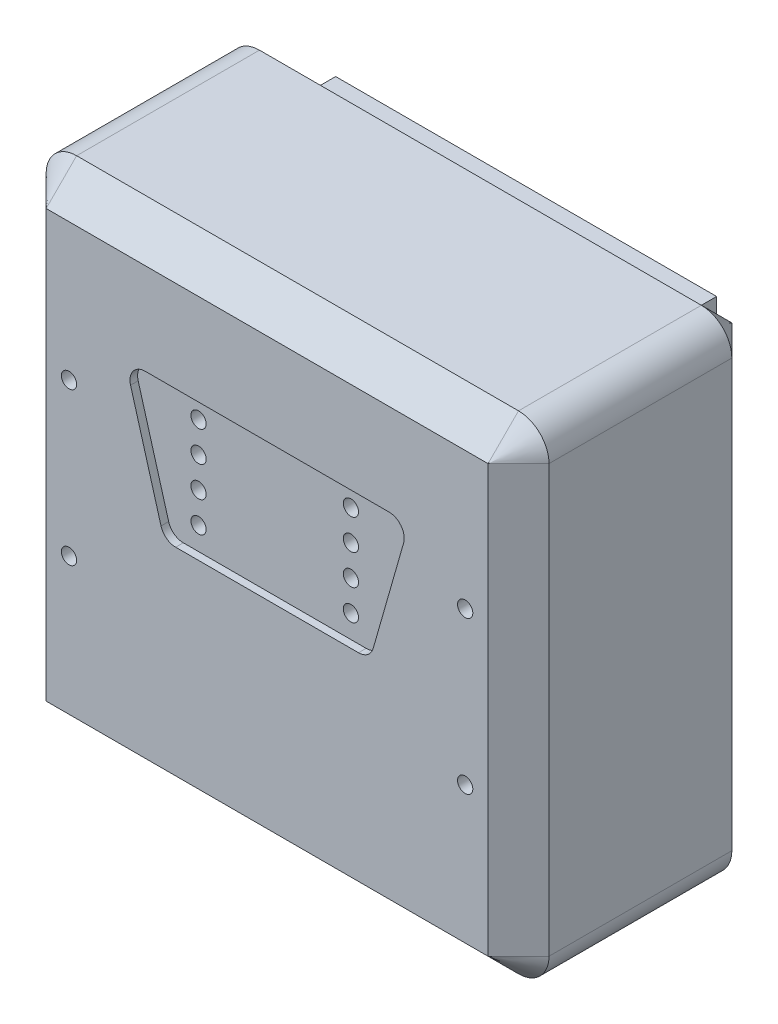
SolidWorks part; units mm, degrees
material "PE High Density Film"
ref_plane "Front Plane" through (0, 0, 0) normal (0, 0, 1) x (1, 0, 0)
ref_plane "Top Plane" through (0, 0, 0) normal (0, 1, 0) x (1, 0, 0)
ref_plane "Right Plane" through (0, 0, 0) normal (1, 0, 0) x (0, 0, -1)
sketch "Sketch1" plane through (0, 0, 0) normal (0, 0, 1) x (1, 0, 0)
  line L0 (0, 0) -> (0, 50.8) construction
  line L1 (-79.375, 50.8) -> (79.375, 50.8)
  line L2 (-79.375, 0) -> (79.375, 0)
  line L3 (79.375, 0) -> (79.375, 50.8)
  line L4 (28.575, 50.8) -> (28.575, 0) construction
  line L5 (28.575, 25.4) -> (79.375, 25.4) construction
  line L6 (53.975, 25.4) -> (53.975, 50.8) construction
  line L7 (53.975, 25.4) -> (53.975, 0) construction
  line L8 (-53.975, 25.4) -> (-53.975, 0) construction
  line L9 (-53.975, 25.4) -> (-53.975, 50.8) construction
  line L10 (-28.575, 25.4) -> (-79.375, 25.4) construction
  line L11 (-28.575, 50.8) -> (-28.575, 0) construction
  line L12 (-79.375, 0) -> (-79.375, 50.8)
  circle A2 centre (53.975, 38.1) radius 1.5875
  circle A3 centre (53.975, 12.7) radius 1.5875
  circle A4 centre (-53.975, 12.7) radius 1.5875
  circle A5 centre (-53.975, 38.1) radius 1.5875
  circle A6 centre (0, 25.4) radius 1.5875
  dimension "D4" = 3.175
  dimension "D5" = 3.175
  dimension "D1" = 50.8
  dimension "D2" = 28.575
  dimension "D3" = 50.8
extrude "Boss-Extrude1" add sketch "Sketch1" along normal blind 6.35
sketch "Sketch2" plane through (0, 0, 6.35) normal (0, 0, 1) x (1, 0, 0)
  line L0 (79.375, 50.8) -> (-79.375, 50.8) construction
  line L1 (-92.075, -139.7) -> (92.075, -139.7)
  line L2 (-104.775, -127) -> (-104.775, 50.8)
  line L3 (-92.075, 63.5) -> (92.075, 63.5)
  line L4 (104.775, -127) -> (104.775, 50.8)
  line L5 (-79.375, 50.8) -> (-79.375, 0) construction
  line L6 (79.375, 0) -> (79.375, 50.8) construction
  arc A0 (-92.075, -139.7) -> (-104.775, -127) centre (-92.075, -127) cw
  arc A1 (92.075, -139.7) -> (104.775, -127) centre (92.075, -127) ccw
  arc A2 (92.075, 63.5) -> (104.775, 50.8) centre (92.075, 50.8) cw
  arc A3 (-104.775, 50.8) -> (-92.075, 63.5) centre (-92.075, 50.8) cw
  point P12 (-104.775, -139.7)
  point P19 (-104.775, 63.5)
  dimension "D5" = 12.7
  dimension "D1" = 12.7
  dimension "D2" = 25.4
  dimension "D3" = 25.4
  dimension "D4" = 203.2
extrude "Boss-Extrude2" add sketch "Sketch2" along normal blind 101.6
chamfer "Chamfer1" distance 12.7 angle 45 16 edges at (0, 63.5, 107.95) (-101.0553, 59.7803, 107.95) (101.0553, 59.7803, 107.95) (-104.775, -38.1, 107.95) (104.775, -38.1, 107.95) (-101.0553, -135.9803, 107.95) (101.0553, -135.9803, 107.95) (0, -139.7, 107.95) (-104.775, -38.1, 6.35) (-101.0553, -135.9803, 6.35) (-101.0553, 59.7803, 6.35) (0, -139.7, 6.35) (0, 63.5, 6.35) (101.0553, -135.9803, 6.35) (101.0553, 59.7803, 6.35) (104.775, -38.1, 6.35)
sketch "Sketch3" plane through (0, 0, 107.95) normal (0, 0, 1) x (1, 0, 0)
  line L0 (0, -127) -> (0, 50.8) construction
  line L1 (-92.075, -127) -> (92.075, -127) construction
  line L2 (92.075, 50.8) -> (-92.075, 50.8) construction
  line L3 (92.075, -38.1) -> (-92.075, -38.1) construction
  line L4 (-92.075, 50.8) -> (-92.075, -127) construction
  circle A0 centre (-82.55, -6.35) radius 3.175
  circle A1 centre (-82.55, -69.85) radius 3.175
  circle A2 centre (82.55, -69.85) radius 3.175
  circle A3 centre (82.55, -6.35) radius 3.175
  point P17 (0, -38.1)
  dimension "D1" = 6.35
  dimension "D2" = 31.75
  dimension "D3" = 82.55
extrude "Cut-Extrude3" cut sketch "Sketch3" against normal blind 31.75
sketch "Sketch4" plane through (0, 0, 107.95) normal (0, 0, 1) x (1, 0, 0)
  line L0 (0, 50.8) -> (0, -127) construction
  line L1 (92.075, 50.8) -> (-92.075, 50.8) construction
  line L2 (-92.075, -127) -> (92.075, -127) construction
  line L3 (92.075, -38.1) -> (-92.075, -38.1) construction
  line L5 (92.075, -127) -> (92.075, 50.8) construction
  line L6 (-92.075, 50.8) -> (-92.075, -127) construction
  line L7 (50.8, 12.7) -> (-50.8, 12.7)
  line L8 (-56.9057, 4.6055) -> (-44.2057, -39.8445)
  line L9 (-38.1, -44.45) -> (38.1, -44.45)
  line L10 (56.9057, 4.6055) -> (44.2057, -39.8445)
  arc A0 (-44.2057, -39.8445) -> (-38.1, -44.45) centre (-38.1, -38.1) ccw
  arc A1 (-50.8, 12.7) -> (-56.9057, 4.6055) centre (-50.8, 6.35) ccw
  arc A2 (44.2057, -39.8445) -> (38.1, -44.45) centre (38.1, -38.1) cw
  arc A3 (50.8, 12.7) -> (56.9057, 4.6055) centre (50.8, 6.35) cw
  point P21 (0, -44.45)
  point P26 (0, 12.7)
  dimension "D1" = 6.35
  dimension "D2" = 50.8
  dimension "D3" = 38.1
  dimension "D4" = 6.35
  dimension "D5" = 50.8
extrude "Cut-Extrude4" cut sketch "Sketch4" against normal blind 3.175
sketch "Sketch5" plane through (0, 0, 104.775) normal (0, 0, 1) x (1, 0, 0)
  line L0 (0, 12.7) -> (0, -44.45) construction
  line L1 (50.8, 12.7) -> (-50.8, 12.7) construction
  line L2 (-38.1, -44.45) -> (38.1, -44.45) construction
  circle A0 centre (-31.75, 3.175) radius 3.175
  circle A1 centre (-31.75, -9.525) radius 3.175
  circle A2 centre (-31.75, -22.225) radius 3.175
  circle A3 centre (-31.75, -34.925) radius 3.175
  circle A4 centre (31.75, -34.925) radius 3.175
  circle A5 centre (31.75, -22.225) radius 3.175
  circle A6 centre (31.75, -9.525) radius 3.175
  circle A7 centre (31.75, 3.175) radius 3.175
  dimension "D1" = 6.35
  dimension "D5" = 12.7
  dimension "D2" = 9.525
  dimension "D3" = 31.75
  dimension "D4" = 4
extrude "Cut-Extrude5" cut sketch "Sketch5" against normal blind 12.7 contours A7 | A5 | A4 | A6 | A1 | A2 | A3 | A0
sketch "Sketch6" plane through (0, 0, 6.35) normal (0, 0, -1) x (-1, 0, 0)
  line L0 (0, -127) -> (0, 0) construction
  line L1 (-92.075, -127) -> (92.075, -127) construction
  circle A0 centre (0, -101.6) radius 6.35
  dimension "D1" = 12.7
  dimension "D2" = 25.4
extrude "Boss-Extrude3" add sketch "Sketch6" along normal blind 29.845
sketch "Sketch7" plane through (0, 0, -23.495) normal (0, 0, -1) x (-1, 0, 0)
  line L0 (-4.445, -106.1348) -> (4.445, -106.1348)
  line L1 (4.445, -106.1348) -> (4.445, -97.0652)
  arc A2 (-4.445, -106.1348) -> (4.445, -97.0652) centre (0, -101.6) cw
  circle A3 centre (0, -101.6) radius 6.35 construction
  circle A4 centre (0, -101.6) radius 6.35 construction
  dimension "D1" = 4.445
extrude "Boss-Extrude4" add sketch "Sketch7" along normal blind 6.35
sketch "Sketch8" plane through (0, 0, -29.845) normal (0, 0, -1) x (-1, 0, 0)
  circle A0 centre (0, -101.6) radius 6.35
  dimension "D1" = 12.7
extrude "Boss-Extrude5" add sketch "Sketch8" along normal blind 12.7
